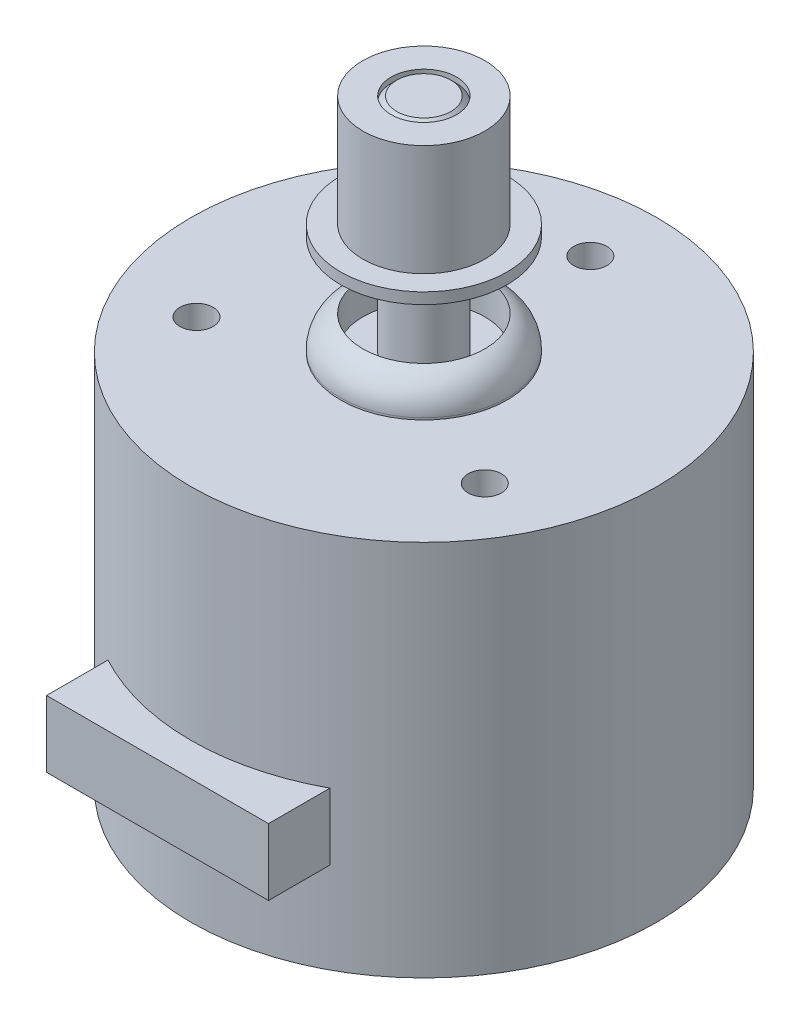
SolidWorks part; units mm, degrees
ref_plane "Front Plane" through (0, 0, 0) normal (0, 0, 1) x (1, 0, 0)
ref_plane "Top Plane" through (0, 0, 0) normal (0, 1, 0) x (1, 0, 0)
ref_plane "Right Plane" through (0, 0, 0) normal (1, 0, 0) x (0, 0, -1)
sketch "Sketch1" plane through (0, 0, 0) normal (0, 1, 0) x (1, 0, 0)
  line L0 (0, 40.1578) -> (0, -40.1578) construction
  line L1 (-36.1819, 0) -> (33.7463, 0) construction
  line L2 (-10, -18.4662) -> (-10, -24)
  line L3 (-10, -24) -> (10, -24)
  line L4 (10, -18.4662) -> (10, -24)
  line L5 (0, 0) -> (-25.9808, -15) construction
  line L6 (0, 0) -> (25.9808, -15) construction
  circle A0 centre (0, 0) radius 21
  circle A1 centre (0, 0) radius 5.5
  circle A2 centre (0, 0) radius 2.945
  circle A3 centre (0, 0) radius 7.5
  circle A4 centre (0, 0) radius 15 construction
  circle A5 centre (0, 15) radius 1.5
  circle A6 centre (-12.9904, -7.5) radius 1.5
  circle A7 centre (12.9904, -7.5) radius 1.5
  point P10 (0, 0)
  point P15 (0, -24)
  point P19 (-12.9904, -7.5)
  point P22 (12.9904, -7.5)
  dimension "D1" = 42
  dimension "D2" = 20
  dimension "D4" = 15
  dimension "D5" = 11
  dimension "D6" = 5.89
  dimension "D7" = 30
  dimension "D8" = 120
  dimension "D10" = 3
  dimension "D11" = 3
  dimension "D12" = 3
  dimension "D3" = 24
  dimension "D9" = 120
extrude "Boss-Extrude1" add sketch "Sketch1" along normal mid plane 34 contours A2 | A1 A2 | A3 A1 | A0 A7 A6 A5 A3 | A6 | A7 | A5 region at (-10.4431, 0, -17.5313) region at (-5.3444, 0, 0) region at (0, 0, 0) region at (-7.2879, 0, 0) region at (0, 0, -15) region at (-12.9904, 0, 7.5) region at (12.9904, 0, 7.5)
extrude "Cut-Extrude1" cut sketch "Sketch1<3>" against normal blind 10 from surface contours A6 | A7 | A5 region at (0, 0, -15) region at (-12.9904, 0, 7.5) region at (12.9904, 0, 7.5) starting at face at (0, 17, 21)
sketch "Sketch1<3>" plane through (0, 0, 0) normal (0, 1, 0) x (1, 0, 0) same geometry as "Sketch1"
extrude "Boss-Extrude2" add sketch "Sketch1<4>" along normal blind 3 from surface contours A3 A1 region at (-7.2879, 0, 0) starting at face at (-12.9904, 17, 9)
sketch "Sketch1<4>" plane through (0, 0, 0) normal (0, 1, 0) x (1, 0, 0) same geometry as "Sketch1"
fillet "Fillet1" radius 3 1 edges at (0, 20, 7.5)
extrude "Boss-Extrude3" add sketch "Sketch1<5>" along normal blind 20 from surface contours A2 region at (0, 0, 0) starting at face at (0, 17, 7.5)
sketch "Sketch1<5>" plane through (0, 0, 0) normal (0, 1, 0) x (1, 0, 0) same geometry as "Sketch1"
extrude "Boss-Extrude4" add sketch "Sketch1<8>" along normal blind 6 from offset 8.8 contours A0 L2 L3 L4 region at (0, 0, 22.0152) offset against normal yes
sketch "Sketch1<8>" plane through (0, 0, 0) normal (0, 1, 0) x (1, 0, 0) same geometry as "Sketch1"
chamfer "Chamfer1" distance 0.5 angle 45 1 edges at (0, 37, 2.945)
extrude "Boss-Extrude6" add sketch "Sketch1<10>" against normal blind 10 from surface contours A1 A2 region at (-5.3444, 0, 0) starting at face at (0, 37, 2.445)
sketch "Sketch1<10>" plane through (0, 0, 0) normal (0, 1, 0) x (1, 0, 0) same geometry as "Sketch1"
extrude "Boss-Extrude7" add sketch "Sketch1<12>" against normal blind 1 from surface contours A1 A2 | A3 A1 region at (-5.3444, 0, 0) region at (-7.2879, 0, 0) starting at face at (0, 27, 2.945)
sketch "Sketch1<12>" plane through (0, 0, 0) normal (0, 1, 0) x (1, 0, 0) same geometry as "Sketch1"
